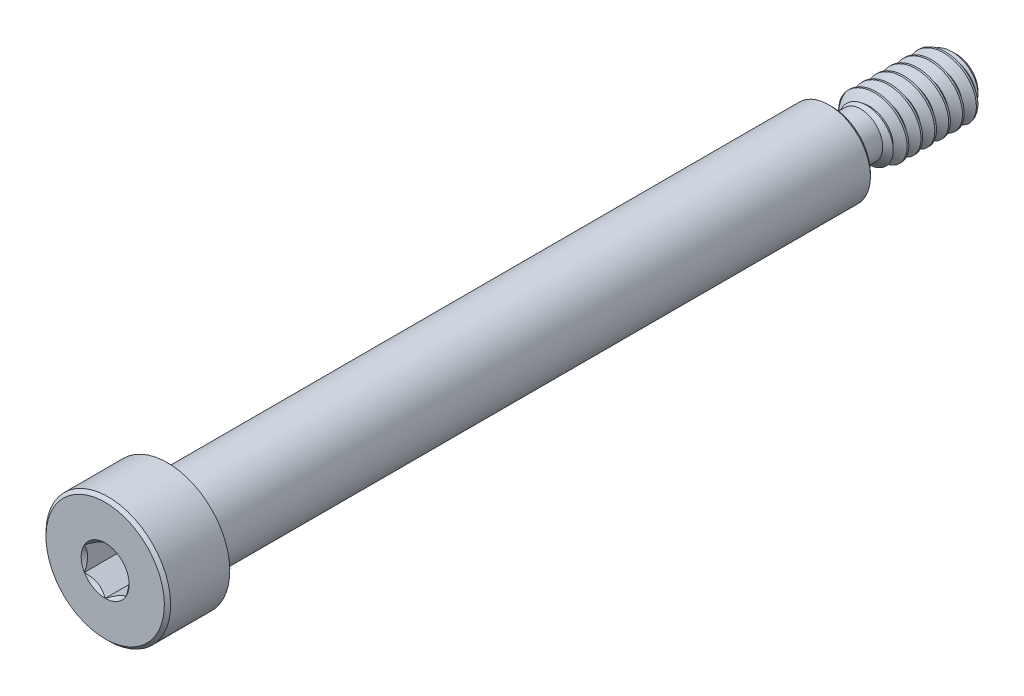
SolidWorks part; units mm, degrees
material "Nylon 101"
ref_plane "Front Plane" through (0, 0, 0) normal (0, 0, 1) x (1, 0, 0)
ref_plane "Top Plane" through (0, 0, 0) normal (0, 1, 0) x (1, 0, 0)
ref_plane "Right Plane" through (0, 0, 0) normal (1, 0, 0) x (0, 0, -1)
sketch "Sketch2" plane through (0, 0, 0) normal (1, 0, 0) x (0, 0, -1)
  line L0 (-32.5438, 0) -> (32.5438, 0) construction
  line L1 (-32.5438, 0) -> (-32.5438, 4.7625)
  line L2 (-32.5438, 4.7625) -> (-27.7812, 4.7625)
  line L3 (-27.7812, 4.7625) -> (-27.7812, 3.175)
  line L4 (-27.7812, 3.175) -> (23.0187, 3.175)
  line L5 (23.0187, 2.413) -> (32.5437, 2.413)
  line L6 (32.5437, 2.413) -> (32.5438, 0)
  line L7 (32.4776, 2.5276) -> (33.0068, 1.611) construction
  line L8 (33.0068, 1.611) -> (33.5359, 2.5276) construction
  line L9 (33.5359, 2.5276) -> (32.4776, 2.5276) construction
  line L10 (32.5437, 2.413) -> (33.4698, 2.413) construction
  line L11 (33.0068, 2.5276) -> (33.0068, 2.413) construction
  line L12 (33.0068, 2.413) -> (33.0068, 1.7256) construction
  line L13 (33.0068, 1.7256) -> (33.0068, 1.611) construction
  line L14 (32.9406, 1.7256) -> (33.0729, 1.7256)
  line L15 (32.5107, 2.4703) -> (33.5029, 2.4703)
  line L16 (33.0729, 1.7256) -> (33.5029, 2.4703)
  line L17 (32.9406, 1.7256) -> (32.5107, 2.4703)
  line L18 (32.5438, 0) -> (32.5437, -2.413) construction
  line L19 (23.0187, -3.175) -> (23.0187, 0) construction
  line L20 (23.0187, 0) -> (23.0187, 3.175) construction
  line L21 (-32.5438, 0) -> (-32.5437, -4.7625) construction
  line L22 (25.1952, 1.6891) -> (25.1952, -1.6891) construction
  line L23 (32.5438, 0) -> (25.1952, 0) construction
  ellipse E0 centre (28.8695, 0) end of major axis (30.2982, 0) minor radius 0.9652 construction
  point P12 (29.8979, -2.413)
  point P22 (33.0068, 2.4703)
  point P23 (21.1137, 0)
  point P25 (-21.1138, 0)
  point P26 (-27.7812, -4.7625)
  point P29 (23.0187, -3.175)
  point P40 (25.1952, 0)
  dimension "D1" = 2.6458
  dimension "D3" = 11.43
  dimension "D4" = 11.43
  dimension "Shoulder Length" = 50.8
  dimension "D5" = 1.9304
  dimension "D6" = 2.8575
sketch "Sketch3" plane through (0, 0, 0) normal (0, 0, 1) x (1, 0, 0)
  line L1 (0, 1.8331) -> (-1.5875, 0.9165)
  line L2 (-1.5875, 0.9165) -> (-1.5875, -0.9165)
  line L3 (-1.5875, -0.9165) -> (0, -1.8331)
  line L4 (0, -1.8331) -> (1.5875, -0.9165)
  line L5 (1.5875, -0.9165) -> (1.5875, 0.9165)
  line L6 (1.5875, 0.9165) -> (0, 1.8331)
  circle A0 centre (0, 0) radius 1.5875 construction
  dimension "Drive Size" = 3.175
sketch "Sketch4" plane through (0, 0, 0) normal (1, 0, 0) x (0, 0, -1)
  line L0 (-27.7812, 4.7625) -> (-32.3056, 4.7625)
  line L1 (-32.3056, 4.7625) -> (-32.5438, 4.5244)
  line L2 (-27.7812, 4.7625) -> (-27.7812, 3.175)
  line L7 (-32.5438, 0) -> (32.5438, 0) construction
  line L8 (-27.7812, 3.175) -> (22.7647, 3.175)
  line L9 (22.7647, 3.175) -> (23.0187, 2.921)
  line L10 (23.0187, 2.921) -> (23.0187, 0)
  line L11 (23.0187, 3.175) -> (23.0187, 2.921) construction
  line L12 (23.0187, 2.921) -> (23.0187, 2.667) construction
  line L13 (23.0187, 2.667) -> (23.0187, 2.413) construction
  line L14 (-32.5438, 4.5244) -> (-32.5438, 0)
  line L16 (-32.5438, 0) -> (23.0187, 0)
  line L18 (-32.5438, 4.7625) -> (-27.7812, 4.7625) construction
  dimension "D3" = 45
  dimension "D5" = 9.0487
  dimension "D1" = 45
revolve "Revolve1" add sketch "Sketch4" angle 360 about L16
sketch "Sketch5" plane through (0, 0, 32.5438) normal (0, 0, 1) x (1, 0, 0)
  line L0 (1.5875, 0.9165) -> (0, 1.8331) construction
  line L1 (1.5875, -0.9165) -> (1.5875, 0.9165) construction
  line L2 (0, -1.8331) -> (1.5875, -0.9165) construction
  line L3 (-1.5875, -0.9165) -> (0, -1.8331) construction
  line L4 (-1.5875, 0.9165) -> (-1.5875, -0.9165) construction
  line L5 (0, 1.8331) -> (-1.5875, 0.9165) construction
  line L6 (1.5875, 0.9165) -> (0, 1.8331)
  line L7 (1.5875, -0.9165) -> (1.5875, 0.9165)
  line L8 (0, -1.8331) -> (1.5875, -0.9165)
  line L9 (-1.5875, -0.9165) -> (0, -1.8331)
  line L10 (-1.5875, 0.9165) -> (-1.5875, -0.9165)
  line L11 (0, 1.8331) -> (-1.5875, 0.9165)
extrude "Cut-Extrude1" cut sketch "Sketch5" against normal blind 3.5719
sketch "Sketch6" plane through (0, 0, 32.5438) normal (0, 0, 1) x (1, 0, 0)
  circle A0 centre (0, 0) radius 1.8331
extrude "Cut-Extrude4" cut sketch "Sketch6" against normal blind 3.5719 draft 45
sketch "Sketch7" plane through (0, 0, 0) normal (1, 0, 0) x (0, 0, -1)
  line L0 (23.0187, 2.413) -> (31.75, 2.413)
  line L1 (23.0187, 2.413) -> (32.5437, 2.413) construction
  line L2 (31.75, 2.413) -> (32.5437, 1.6192)
  line L3 (32.5437, 2.413) -> (32.5437, 0) construction
  line L4 (32.5437, 1.6192) -> (32.5438, 0)
  line L5 (32.5438, 0) -> (23.0187, 0)
  line L6 (23.0187, -2.921) -> (23.0187, 2.921) construction
  line L7 (23.0187, 0) -> (23.0187, 2.413)
  dimension "D1" = 45
  dimension "D2" = 0.7938
revolve "Revolve2" add sketch "Sketch7" angle 360 about L5
sketch "Sketch10" plane through (0, 0, 0) normal (1, 0, 0) x (0, 0, -1)
  line L0 (23.3807, 1.6891) -> (25.1952, 1.6891)
  line L1 (25.1952, 1.6891) -> (26.6811, 3.175)
  line L2 (26.6811, 3.175) -> (23.0187, 3.175)
  line L3 (23.0187, 3.175) -> (23.0187, 2.051)
  line L5 (32.5438, 0) -> (23.0187, 0) construction
  line L6 (-32.5438, 0) -> (32.5438, 0) construction
  line L7 (-27.7812, 3.175) -> (23.0187, 3.175) construction
  line L12 (-27.7812, 3.175) -> (-27.4637, 3.175)
  line L13 (-27.7812, 3.175) -> (-27.7812, 3.0162)
  line L14 (-27.7812, 3.0162) -> (-27.6225, 3.0162)
  line L15 (-27.4637, 3.175) -> (-27.6225, 3.0162)
  line L16 (23.3807, 1.6891) -> (23.3807, 2.051) construction
  line L17 (23.3807, 2.051) -> (23.3807, 2.413) construction
  line L18 (31.75, 2.413) -> (23.0187, 2.413) construction
  arc A0 (23.0187, 2.051) -> (23.3807, 1.6891) centre (23.3807, 2.051) ccw
  dimension "D3" = 45
  dimension "D4" = 45
  dimension "D5" = 6.0325
revolve "Cut-Revolve1" cut sketch "Sketch10" angle 360 about L5
fillet "Fillet1" radius 0.0794 1 edges at (0, 3.0162, 27.7812)
sketch "Sketch15" plane through (0, 0, 0) normal (0, 0, 1) x (1, 0, 0)
  circle A0 centre (0, 0) radius 4.7625 construction
sketch "Sketch8" plane through (0, 0, -32.5437) normal (0, 0, -1) x (-1, 0, 0)
  circle A1 centre (0, 0) radius 2.413
curve "Helix/Spiral1" pitch 1.0583 height 8.4069 radius 2.413 centre (0, 0, -32.5437) axis (0, 0, 1) start towards (0, 1, 0)
sketch "Sketch9" plane through (0, 0, 0) normal (1, 0, 0) x (0, 0, -1)
  line L0 (32.9406, 1.7256) -> (33.0729, 1.7256) construction
  line L1 (33.0729, 1.7256) -> (33.5029, 2.4703) construction
  line L2 (32.5107, 2.4703) -> (33.5029, 2.4703) construction
  line L3 (32.9406, 1.7256) -> (32.5107, 2.4703) construction
  line L4 (32.9406, 1.7256) -> (33.0729, 1.7256)
  line L5 (33.0729, 1.7256) -> (33.5029, 2.4703)
  line L6 (32.5107, 2.4703) -> (33.5029, 2.4703)
  line L7 (32.9406, 1.7256) -> (32.5107, 2.4703)
sweep "Cut-Sweep1" cut profiles "Sketch9" path "Helix/Spiral1"
equation "\"D2@Sketch2\" = \"Pitch@Sketch2\" / 8"
equation "\"D1@Sketch2\"=\"Pitch@Sketch2\"*2.5"
equation "\"D5@Sketch4\"=\"Head Diameter@Sketch2\"*0.95"
equation "\"D1@Cut-Extrude1\"=\"Head Height@Sketch2\"*0.75"
equation "\"D1@Cut-Extrude4\"=\"D1@Cut-Extrude1\""
equation "\"D2@Sketch7\" = \"Pitch@Sketch2\" * 0.75"
equation "\"D3@Helix/Spiral1\"=\"Thread Length@Sketch2\"-\"Flat@Sketch2\"+\"Pitch@Sketch2\""
equation "\"D4@Helix/Spiral1\"=\"Pitch@Sketch2\""
equation "\"D3@Sketch2\"=\"Thread Length@Sketch2\"*1.2"
equation "\"D4@Sketch2\"=\"D3@Sketch2\""
equation "\"D5@Sketch2\"=\"Screw Size Decimal Equivalent@Sketch2\"*.4"
equation "\"D6@Sketch2\"=\"Thread Length@Sketch2\"*.3"
equation "\"Flat@Sketch2\"=\"Thread Length@Sketch2\"*0.2285"
equation "\"Flat OD@Sketch2\"= \"Screw Size Decimal Equivalent@Sketch2\" * .7"
equation "\"D5@Sketch10\"=\"Shoulder Diameter@Sketch2\"*.95"
equation "\"D1@Fillet1\"=\"Shoulder Diameter@Sketch2\"*.0125"
